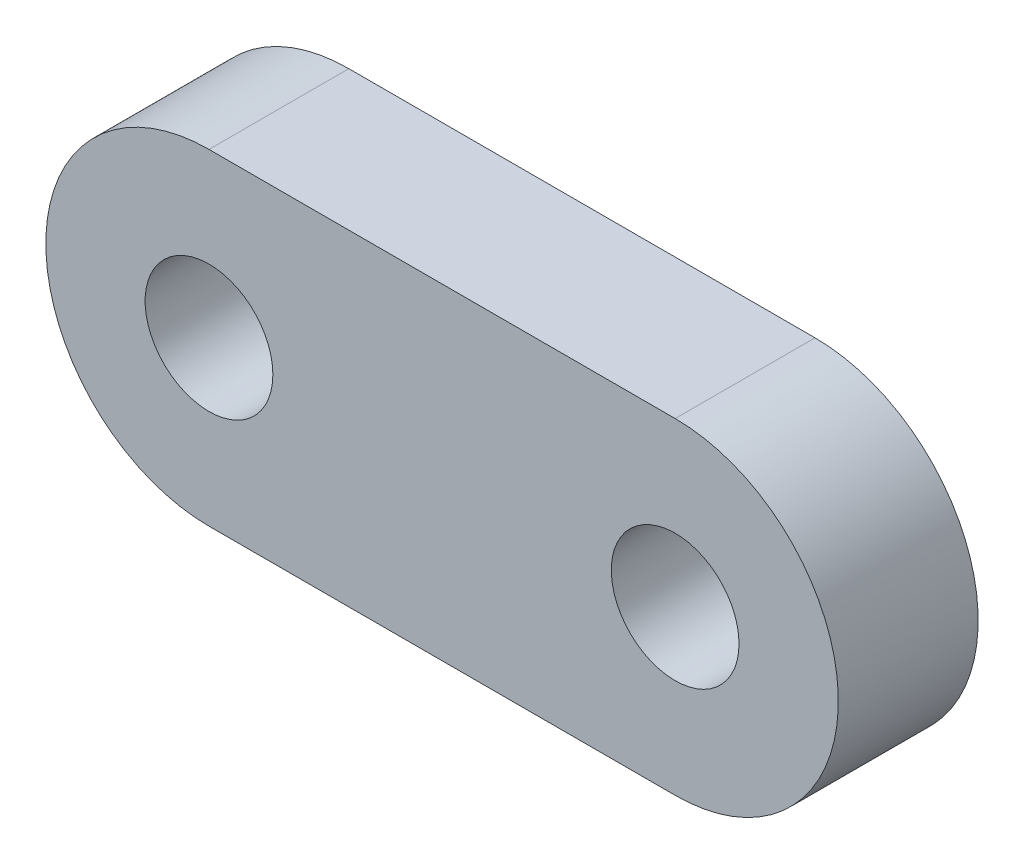
SolidWorks part; units mm, degrees
ref_plane "Front Plane" through (0, 0, 0) normal (0, 0, 1) x (1, 0, 0)
ref_plane "Top Plane" through (0, 0, 0) normal (0, 1, 0) x (1, 0, 0)
ref_plane "Right Plane" through (0, 0, 0) normal (1, 0, 0) x (0, 0, -1)
sketch "Sketch1" plane through (0, 0, 0) normal (0, 0, 1) x (1, 0, 0)
  line L0 (0, 0) -> (12.7, 0) construction
  line L1 (0, 4.445) -> (12.7, 4.445)
  line L2 (0, -4.445) -> (12.7, -4.445)
  arc A0 (0, 4.445) -> (0, -4.445) centre (0, 0) ccw
  arc A1 (12.7, -4.445) -> (12.7, 4.445) centre (12.7, 0) ccw
  point P3 (6.35, 0)
  dimension "D1" = 4.445
  dimension "D2" = 12.7
extrude "Boss-Extrude1" add sketch "Sketch1" along normal blind 3.81
sketch "Sketch2" plane through (0, 0, 3.81) normal (0, 0, 1) x (1, 0, 0)
  circle A0 centre (0, 0) radius 1.7399
  dimension "D1" = 3.4798
extrude "Cut-Extrude1" cut sketch "Sketch2" against normal through all both and the other way through all
ref_plane "Plane1" through (6.35, 0, 0) normal (1, 0, 0) x (0, 0, -1)
mirror "Mirror1" about plane through (6.35, 0, 0) normal (1, 0, 0) of "Cut-Extrude1"
